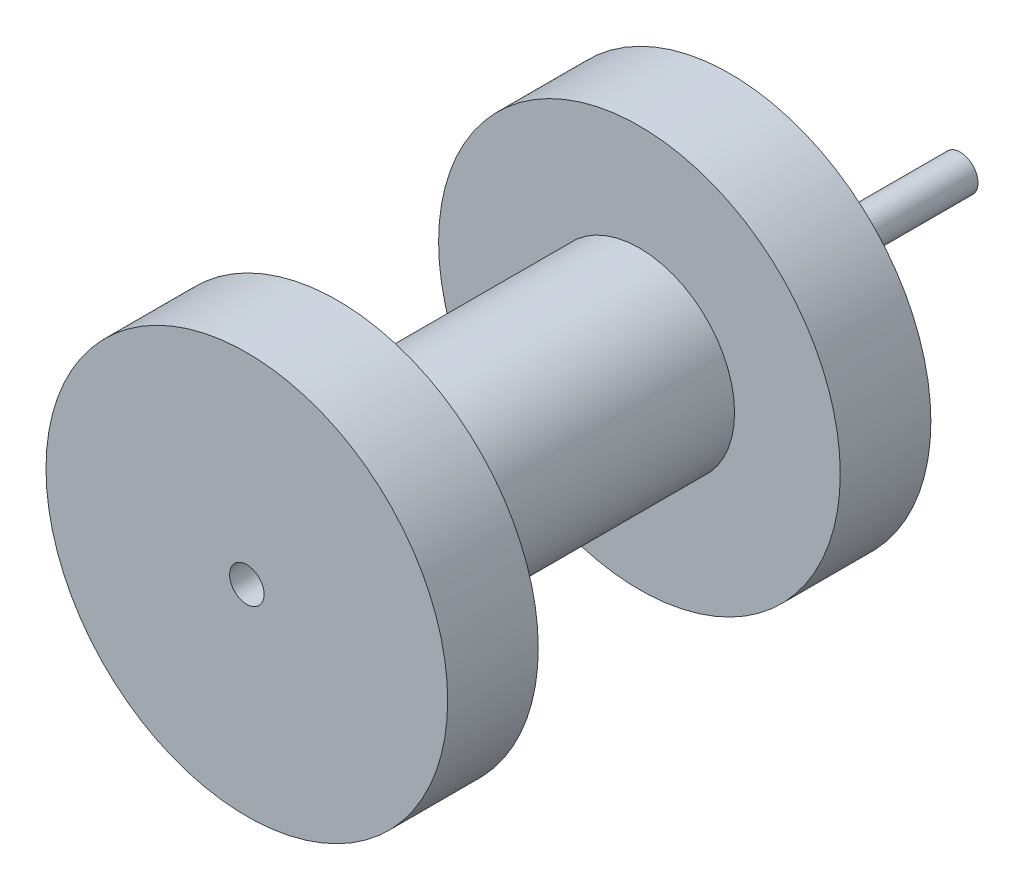
SolidWorks part; units mm, degrees
ref_plane "Front Plane" through (0, 0, 0) normal (0, 0, 1) x (1, 0, 0)
ref_plane "Top Plane" through (0, 0, 0) normal (0, 1, 0) x (1, 0, 0)
ref_plane "Right Plane" through (0, 0, 0) normal (1, 0, 0) x (0, 0, -1)
sketch "Sketch1" plane through (0, 0, 0) normal (0, 0, 1) x (1, 0, 0)
  circle A0 centre (0, 0) radius 1.5001
extrude "Boss-Extrude1" add sketch "Sketch1" along normal mid plane 59.9948
shell "Shell3" thickness 0.0508 removed face at (1.5001, 0, -29.9974) removed face at (1.5001, 0, 29.9974)
ref_plane "Plane2" through (0, 0, -31.875) normal (0, 0, 1) x (1, 0, 0)
ref_plane "Plane3" through (0, 0, 29.9974) normal (0, 0, 1) x (1, 0, 0)
sketch "Sketch5" plane through (0, 0, 29.9974) normal (0, 0, 1) x (1, 0, 0)
  circle A0 centre (0, 0) radius 1.4493
  circle A1 centre (0, 0) radius 16.891
extrude "Boss-Extrude8" add sketch "Sketch5" against normal blind 7.62
ref_plane "Plane5" through (0, 0, 22.3774) normal (0, 0, -1) x (-1, 0, 0)
sketch "Sketch6" plane through (0, 0, 22.3774) normal (0, 0, -1) x (-1, 0, 0)
  circle A0 centre (0, 0) radius 7.62
  circle A1 centre (0, 0) radius 8
extrude "Boss-Extrude9" add sketch "Sketch6" along normal blind 25.4
ref_plane "Plane6" through (0, 0, -3.0226) normal (0, 0, -1) x (-1, 0, 0)
sketch "Sketch7" plane through (0, 0, -3.0226) normal (0, 0, -1) x (-1, 0, 0)
  circle A0 centre (0, 0) radius 1.5001
  circle A1 centre (0, 0) radius 16.891
extrude "Boss-Extrude10" add sketch "Sketch7" along normal blind 7.62
sketch "Sketch8" plane through (0, 0, 29.9974) normal (0, 0, 1) x (1, 0, 0)
  circle A0 centre (0, 0) radius 1.4493
  circle A1 centre (0, 0) radius 8
extrude "Boss-Extrude11" add sketch "Sketch8" against normal blind 2.54
